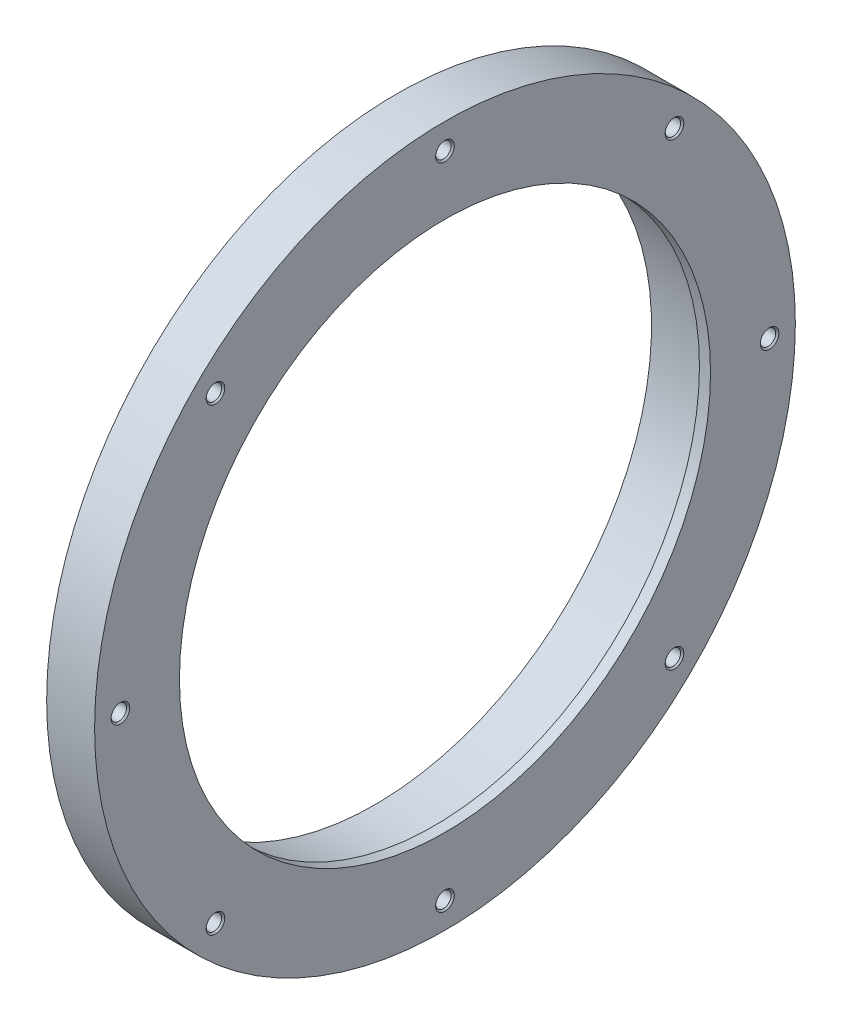
SolidWorks part; units mm, degrees
material "Stop 1060"
ref_plane "Płaszczyzna przednia" through (0, 0, 0) normal (0, 0, 1) x (1, 0, 0)
ref_plane "Płaszczyzna górna" through (0, 0, 0) normal (0, 1, 0) x (1, 0, 0)
ref_plane "Płaszczyzna prawa" through (0, 0, 0) normal (1, 0, 0) x (0, 0, -1)
sketch "Szkic1" plane through (0, 0, 0) normal (0, 0, 1) x (1, 0, 0)
  line L0 (0, 0) -> (67.9681, 0) construction
  line L16 (19, 95) -> (6, 95)
  line L17 (6, 80) -> (0, 80)
  line L18 (16, 75) -> (0, 75)
  line L19 (16, 72) -> (19, 72)
  line L20 (16, 72) -> (16, 75)
  line L21 (19, 95) -> (19, 72)
  line L22 (0, 80) -> (0, 75)
  line L23 (6, 80) -> (6, 95)
  dimension "D1" = 6
  dimension "D2" = 13
  dimension "D3" = 95
  dimension "D4" = 80
  dimension "D5" = 3
  dimension "D6" = 72
  dimension "D7" = 75
revolve "Obrót1" add sketch "Szkic1" angle 360 about L0
hole_wizard "Otwór gwintowany M51" positions "Szkic3" profile "Szkic5" tap size "M5" standard "DIN" end condition through all
sketch "Szkic3" plane through (19, 0, 0) normal (1, 0, 0) x (0, 0, -1)
  point P0 (0, 88)
  point P12 (62.2254, 62.2254)
  point P13 (88, 0)
  point P14 (62.2254, -62.2254)
  point P15 (0, -88)
  point P16 (-62.2254, -62.2254)
  point P17 (-88, 0)
  point P18 (-62.2254, 62.2254)
  point P19 (0, 0)
  dimension "D1" = 88
  dimension "D2" = 8
sketch "Szkic5" plane through (19, 88, 0) normal (0, 1, 0) x (0, 0, -1)
  line L0 (0, 0) -> (0, 19)
  line L1 (0, 19) -> (2.1, 19)
  line L2 (2.1, 19) -> (2.1, 0.425)
  line L3 (2.1, 0.425) -> (2.525, 0)
  line L5 (2.525, 0) -> (0, 0)
  line L6 (-2.1, 0.425) -> (-2.525, 0) construction
  line L11 (0, -6.35) -> (0, 107.95) construction
  dimension "Średnica otworu gwintowanego na wylot" = 4.2
  dimension "Głębokość otworu gwintowanego na wylot" = 19
  dimension "Średnica zewnętrznego pogłębienia stożkowego" = 5.05
  dimension "Kąt zewnętrznego pogłębienia stożkowego" = 90
cosmetic thread "Gwint otworu1"
cosmetic thread "Gwint otworu2"
cosmetic thread "Gwint otworu3"
cosmetic thread "Gwint otworu4"
cosmetic thread "Gwint otworu5"
cosmetic thread "Gwint otworu6"
cosmetic thread "Gwint otworu7"
cosmetic thread "Gwint otworu8"
